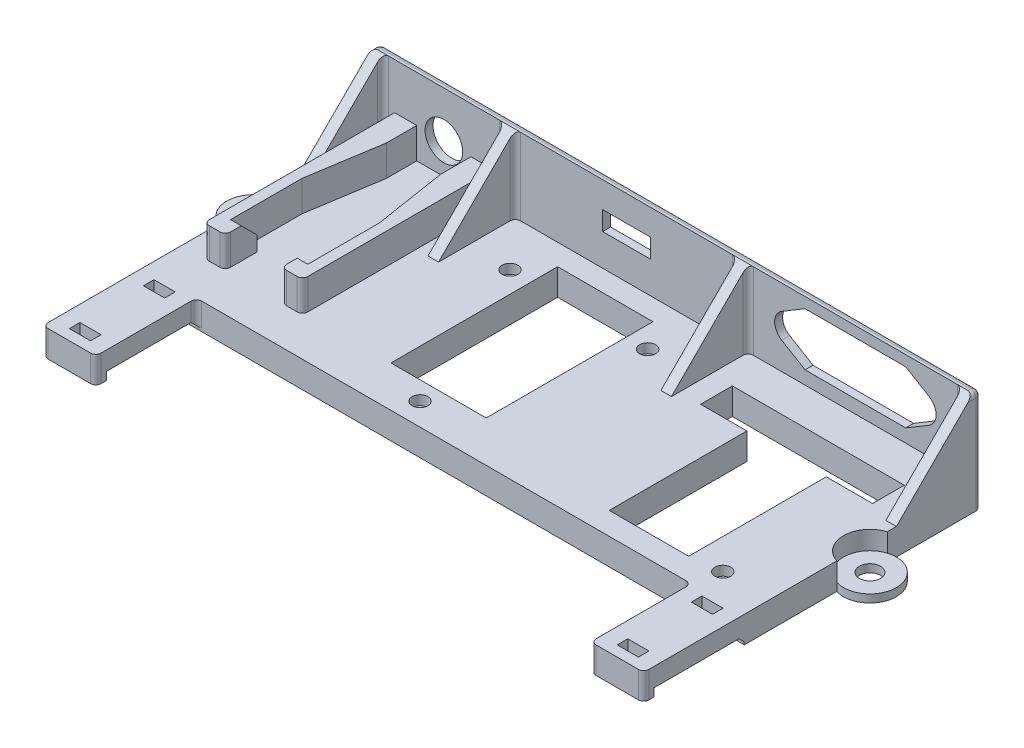
SolidWorks part; units mm, degrees
note: The reader was unsure of these and kept them because the rebuilt part matched: shared geometry of "Sketch1<4>", "Sketch2<3>", "Sketch2<4>", "Sketch2<5>", "Sketch1<5>", "Sketch2<6>", "Sketch4<4>".
ref_plane "Front Plane" through (0, 0, 0) normal (0, 0, 1) x (1, 0, 0)
ref_plane "Top Plane" through (0, 0, 0) normal (0, 1, 0) x (1, 0, 0)
ref_plane "Right Plane" through (0, 0, 0) normal (1, 0, 0) x (0, 0, -1)
sketch "Sketch1" plane through (0, 0, 0) normal (0, 0, 1) x (1, 0, 0)
  line L0 (78.75, 7.5) -> (103.75, 7.5)
  line L1 (0, 0) -> (113.5, 0)
  line L2 (0, 0) -> (0, 14.5)
  line L3 (0, 14.5) -> (113.5, 14.5)
  line L4 (113.5, 0) -> (113.5, 14.5)
  line L5 (100.75, 2.5) -> (105.1621, 5.1402)
  line L6 (75, 14.5) -> (107.5, 14.5)
  line L7 (75, 14.5) -> (75, 0)
  line L8 (75, 0) -> (107.5, 0)
  line L9 (107.5, 14.5) -> (107.5, 0)
  line L10 (81.75, 12.5) -> (100.75, 12.5)
  line L11 (81.75, 12.5) -> (81.75, 2.5)
  line L12 (81.75, 2.5) -> (100.75, 2.5)
  line L13 (100.75, 12.5) -> (100.75, 2.5)
  line L14 (0, 0) -> (113.5, 0)
  line L15 (0, 0) -> (0, -5)
  line L16 (0, -5) -> (113.5, -5)
  line L17 (113.5, 0) -> (113.5, -5)
  line L18 (43.5, 9.6) -> (52.5, 9.6)
  line L19 (43.5, 9.6) -> (43.5, 6)
  line L20 (43.5, 6) -> (52.5, 6)
  line L21 (52.5, 9.6) -> (52.5, 6)
  line L22 (31, 0) -> (65, 0)
  line L23 (31, 0) -> (31, 9.6)
  line L24 (31, 9.6) -> (65, 9.6)
  line L25 (65, 0) -> (65, 9.6)
  line L26 (6, 13) -> (21, 13)
  line L27 (6, 13) -> (6, 0)
  line L28 (6, 0) -> (21, 0)
  line L29 (21, 13) -> (21, 0)
  line L30 (25, 0) -> (27, 0)
  line L31 (25, 0) -> (25, 14.5)
  line L32 (25, 14.5) -> (27, 14.5)
  line L33 (27, 0) -> (27, 14.5)
  line L34 (69, 14.5) -> (71, 14.5)
  line L35 (69, 14.5) -> (69, 0)
  line L36 (69, 0) -> (71, 0)
  line L37 (71, 14.5) -> (71, 0)
  line L38 (0, 14.5) -> (2, 14.5)
  line L39 (0, 14.5) -> (0, 0)
  line L40 (0, 0) -> (2, 0)
  line L41 (2, 14.5) -> (2, 0)
  line L42 (113.5, 14.5) -> (111.5, 14.5)
  line L43 (113.5, 14.5) -> (113.5, 0)
  line L44 (113.5, 0) -> (111.5, 0)
  line L45 (111.5, 14.5) -> (111.5, 0)
  line L46 (100.75, 12.5) -> (105.1621, 9.8598)
  line L47 (81.75, 12.5) -> (77.3379, 9.8598)
  line L48 (81.75, 2.5) -> (77.3379, 5.1402)
  circle A0 centre (78.75, 7.5) radius 1.5
  circle A1 centre (103.75, 7.5) radius 1.5
  circle A2 centre (13.5, 5.8) radius 3.55
  circle A3 centre (103.75, 7.5) radius 2.75
  circle A4 centre (78.75, 7.5) radius 2.75
  point P9 (78.75, 6)
  point P14 (91.25, 7.5)
  point P15 (91.25, 14.5)
  point P20 (81.75, 7.5)
  point P21 (91.25, 12.5)
  point P32 (48, 9.6)
  point P33 (48, 9.6)
  point P36 (13.5, 13)
  point P55 (80.0469, 3.5192)
  dimension "D2" = 3
  dimension "D12" = 7.1
  dimension "D27" = 5.5
  dimension "D1" = 14.5
  dimension "D3" = 6
  dimension "D4" = 25
  dimension "D5" = 32.5
  dimension "D6" = 19
  dimension "D7" = 10
  dimension "D8" = 3.6
  dimension "D9" = 9
  dimension "D10" = 6
  dimension "D11" = 34
  dimension "D13" = 5.8
  dimension "D14" = 13
  dimension "D15" = 15
  dimension "D16" = 2
  dimension "D17" = 2
  dimension "D18" = 2
  dimension "D19" = 4
  dimension "D20" = 5
  dimension "D21" = 4
  dimension "D22" = 4
  dimension "D23" = 4
  dimension "D24" = 4
  dimension "D25" = 4
  dimension "D26" = 2
extrude "Boss-Extrude1" add sketch "Sketch1" against normal blind 1.5
extrude "Boss-Extrude2" add sketch "Sketch1<4>" against normal blind 1.5 and the other way blind 43.25 contours L17 L1 L14 L15 L16
sketch "Sketch1<4>" plane through (0, 0, 0) normal (0, 0, 1) x (1, 0, 0) same geometry as "Sketch1"
sketch "Sketch2" plane through (0, 0, 0) normal (0, 1, 0) x (1, 0, 0)
  line L0 (0, 0) -> (113.5, 0) construction
  line L1 (20.8, 0) -> (6.2, 0)
  line L2 (20.8, 0) -> (20.8, -30)
  line L3 (20.8, -30) -> (6.2, -30)
  line L4 (6.2, 0) -> (6.2, -30)
  line L5 (6, 0) -> (21, 0) construction
  line L6 (35, -9) -> (61, -9)
  line L7 (0, 0) -> (113.5, 0) construction
  line L8 (43.5, 0) -> (52.5, 0) construction
  line L9 (0, 0) -> (113.5, 0) construction
  line L10 (75, 0) -> (107.5, 0)
  line L11 (75, 0) -> (75, -41.3)
  line L12 (75, -41.3) -> (107.5, -41.3)
  line L13 (107.5, 0) -> (107.5, -41.3)
  line L14 (-1.5, -21) -> (115, -21)
  line L15 (0, 1.5) -> (113.5, 1.5) construction
  line L16 (0, 1.5) -> (113.5, 1.5) construction
  line L17 (6.2, -19.5) -> (20.8, -19.5)
  line L18 (39, -4) -> (57, -4)
  line L19 (39, -4) -> (39, -39)
  line L20 (39, -39) -> (57, -39)
  line L21 (57, -4) -> (57, -39)
  line L22 (75, -7) -> (107.5, -7)
  line L23 (75, -7) -> (75, -13)
  line L24 (75, -13) -> (107.5, -13)
  line L25 (107.5, -7) -> (107.5, -13)
  line L26 (83.75, -13) -> (98.75, -13)
  line L27 (83.75, -13) -> (83.75, -39)
  line L28 (83.75, -39) -> (98.75, -39)
  line L29 (98.75, -13) -> (98.75, -39)
  line L30 (8.375, 0) -> (18.625, 0)
  line L31 (8.375, 0) -> (8.375, -5.75)
  line L32 (8.375, -5.75) -> (18.625, -5.75)
  line L33 (18.625, 0) -> (18.625, -5.75)
  line L34 (8.375, -5.75) -> (6.2, -19.5)
  line L35 (18.625, -5.75) -> (20.8, -19.5)
  line L36 (8.2, -34) -> (18.8, -34)
  line L37 (6.2, -34) -> (8.2, -34)
  line L38 (6.2, -34) -> (6.2, -30)
  line L39 (6.2, -30) -> (8.2, -30)
  line L40 (8.2, -34) -> (8.2, -30)
  line L41 (20.8, -34) -> (18.8, -34)
  line L42 (20.8, -34) -> (20.8, -30)
  line L43 (20.8, -30) -> (18.8, -30)
  line L44 (18.8, -34) -> (18.8, -30)
  line L46 (4.2, 0) -> (22.8, 0)
  line L47 (4.2, 0) -> (4.2, -36)
  line L48 (4.2, -36) -> (22.8, -36)
  line L49 (22.8, 0) -> (22.8, -36)
  line L50 (8.2, -34) -> (18.8, -34)
  line L51 (8.2, -34) -> (8.2, -36)
  line L52 (8.2, -36) -> (18.8, -36)
  line L53 (18.8, -34) -> (18.8, -36)
  line L54 (39, -35.5) -> (57, -35.5)
  line L55 (39, -35.5) -> (39, -39)
  line L56 (39, -39) -> (57, -39)
  line L57 (57, -35.5) -> (57, -39)
  circle A0 centre (104.5, -38.3) radius 1.5
  circle A1 centre (35, -9) radius 1.5
  circle A2 centre (61, -9) radius 1.5
  circle A3 centre (48, -39) radius 1.5
  circle A4 centre (-1.5, -21) radius 2
  circle A5 centre (115, -21) radius 2
  circle A6 centre (115, -21) radius 5
  circle A7 centre (-1.5, -21) radius 5
  point P17 (13.5, 0)
  point P20 (13.5, 0)
  point P22 (48, -9)
  point P26 (48, 0)
  point P38 (56.75, 1.5)
  point P39 (56.75, -21)
  point P49 (48, -39)
  point P57 (91.25, -39)
  point P58 (91.25, -41.3)
  point P63 (13.5, 0)
  point P76 (13.5, -36)
  point P77 (13.5, -19.5)
  line M11 (113.5, 0) -> (0, 0)
  line M12 (0, 0) -> (0, -43.25)
  line M14 (113.5, -43.25) -> (113.5, 0)
  dimension "D3" = 3
  dimension "D10" = 4
  dimension "D1" = 14.6
  dimension "D2" = 30
  dimension "D4" = 26
  dimension "D5" = 39
  dimension "D6" = 41.3
  dimension "D7" = 3
  dimension "D8" = 3
  dimension "D9" = 116.5
  dimension "D11" = 22.5
  dimension "D12" = 3
  dimension "D13" = 3
  dimension "D14" = 35
  dimension "D15" = 18
  dimension "D16" = 30
  dimension "D17" = 15
  dimension "D18" = 7
  dimension "D19" = 13
  dimension "D20" = 39
  dimension "D21" = 10.25
  dimension "D22" = 5.75
  dimension "D23" = 10.5
  dimension "D24" = 2
  dimension "D25" = 4
  dimension "D26" = 2
  dimension "D27" = 2
  dimension "D28" = 3.5
extrude "Cut-Extrude1" cut sketch "Sketch2" against normal through all
extrude "Boss-Extrude3" add sketch "Sketch2<3>" against normal up to surface (5 mm away) contours A7 A4 M12 | A6 A5 M14 up to face at (91.25, -5, 18)
sketch "Sketch2<3>" plane through (0, 0, 0) normal (0, 1, 0) x (1, 0, 0) same geometry as "Sketch2"
extrude "Cut-Extrude2" cut sketch "Sketch2<4>" against normal offset from surface (3.5 mm away) 1.5 up to face at (115.25, -5, 21)
sketch "Sketch2<4>" plane through (0, 0, 0) normal (0, 1, 0) x (1, 0, 0) same geometry as "Sketch2"
extrude "Cut-Extrude3" cut sketch "Sketch2<5>" against normal through all contours A4 L14 M12 | L14 A4 M12 | L14 A5 M14 | A5 L14 M14
sketch "Sketch2<5>" plane through (0, 0, 0) normal (0, 1, 0) x (1, 0, 0) same geometry as "Sketch2"
extrude "Boss-Extrude4" add sketch "Sketch1<5>" along normal blind 15 contours L41 L3 L2 L1 | L3 L45 L14 L4 | L33 L32 L31 L30 | L37 L36 L35 L34
sketch "Sketch1<5>" plane through (0, 0, 0) normal (0, 0, 1) x (1, 0, 0) same geometry as "Sketch1"
chamfer "Chamfer1" distance 15 angle 45 4 edges at (112.5, 14.5, 15) (70, 14.5, 15) (26, 14.5, 15) (1, 14.5, 15)
extrude "Boss-Extrude5" add sketch "Sketch2<6>" along normal up to vertex (14.5 mm away) contours L49 L2 L14 M11 | L34 L31 L4 M11 | L47 L14 L4 M11 | L33 L35 L2 M11 | L41 L53 L48 L49 L14 L2 L42 | L51 L37 L38 L4 L14 L47 L48 | L37 L40 L3 L38 | L44 L41 L42 L3
sketch "Sketch2<6>" plane through (0, 0, 0) normal (0, 1, 0) x (1, 0, 0) same geometry as "Sketch2"
sketch "Sketch4" plane through (0, 0, 0) normal (0, 1, 0) x (1, 0, 0)
  line L0 (5, -58.25) -> (5, -46.25)
  line L1 (0, -43.25) -> (10, -43.25)
  line L2 (0, -43.25) -> (0, -62.25)
  line L3 (0, -62.25) -> (10, -62.25)
  line L4 (10, -43.25) -> (10, -62.25)
  line L5 (113.5, -43.25) -> (103.5, -43.25)
  line L6 (113.5, -43.25) -> (113.5, -62.25)
  line L7 (113.5, -62.25) -> (103.5, -62.25)
  line L8 (103.5, -43.25) -> (103.5, -62.25)
  line L9 (3, -46.25) -> (7, -46.25)
  line L10 (3, -46.25) -> (3, -44.25)
  line L11 (3, -44.25) -> (7, -44.25)
  line L12 (7, -46.25) -> (7, -44.25)
  line L13 (3, -58.25) -> (7, -58.25)
  line L14 (3, -58.25) -> (3, -60.25)
  line L15 (3, -60.25) -> (7, -60.25)
  line L16 (7, -58.25) -> (7, -60.25)
  line L17 (108.5, -58.25) -> (108.5, -46.25)
  line L19 (106.5, -46.25) -> (110.5, -46.25)
  line L20 (106.5, -46.25) -> (106.5, -44.25)
  line L21 (106.5, -44.25) -> (110.5, -44.25)
  line L22 (110.5, -46.25) -> (110.5, -44.25)
  line L23 (106.5, -58.25) -> (110.5, -58.25)
  line L24 (106.5, -58.25) -> (106.5, -60.25)
  line L25 (106.5, -60.25) -> (110.5, -60.25)
  line L26 (110.5, -58.25) -> (110.5, -60.25)
  line L27 (0, -62.25) -> (10, -62.25)
  line L28 (0, -62.25) -> (0, -60.25)
  line L29 (0, -60.25) -> (10, -60.25)
  line L30 (10, -62.25) -> (10, -60.25)
  line L31 (113.5, -62.25) -> (103.5, -62.25)
  line L32 (113.5, -62.25) -> (113.5, -60.25)
  line L33 (113.5, -60.25) -> (103.5, -60.25)
  line L34 (103.5, -62.25) -> (103.5, -60.25)
  point P20 (5, -62.25)
  point P21 (108.5, -62.25)
  dimension "D1" = 10
  dimension "D2" = 4
  dimension "D3" = 2
  dimension "D4" = 2
  dimension "D5" = 4
  dimension "D6" = 1
  dimension "D7" = 2
  dimension "D8" = 12
  dimension "D9" = 4
  dimension "D10" = 2
  dimension "D11" = 2
  dimension "D12" = 4
  dimension "D13" = 12
extrude "Boss-Extrude6" add sketch "Sketch4" against normal offset from surface (3.5 mm away) 1.5
extrude "Boss-Extrude7" add sketch "Sketch4<4>" against normal up to surface (5 mm away) contours L29 L2 L3 L4 L15 | L6 L33 L25 L8 L7 up to face at (115, -5, 23)
sketch "Sketch4<4>" plane through (0, 0, 0) normal (0, 1, 0) x (1, 0, 0) same geometry as "Sketch4"
sketch "Sketch5" plane through (0, -3.5, 0) normal (0, -1, 0) x (1, 0, 0)
  line L1 (110.5, 46.25) -> (106.5, 46.25)
  line L2 (110.5, 46.25) -> (110.5, 58.25)
  line L3 (110.5, 58.25) -> (106.5, 58.25)
  line L4 (106.5, 46.25) -> (106.5, 58.25)
  line L5 (7, 46.25) -> (3, 46.25)
  line L6 (7, 46.25) -> (7, 58.25)
  line L7 (7, 58.25) -> (3, 58.25)
  line L8 (3, 46.25) -> (3, 58.25)
extrude "Cut-Extrude4" cut sketch "Sketch5" against normal blind 0.4
chamfer "Chamfer2" distance 1 angle 45 2 edges at (108.5, -3.5, 43.25) (5, -3.5, 43.25)
chamfer "Chamfer3" distance 3 angle 45 2 edges at (7.2, 5.8, 30) (19.8, 5.8, 30)
sketch "Sketch6" plane through (0, -5, 0) normal (0, -1, 0) x (1, 0, 0)
  circle A0 centre (35, 9) radius 3
  circle A1 centre (61, 9) radius 3
  circle A2 centre (48, 39) radius 3
  circle A3 centre (104.5, 38.3) radius 3
  dimension "D1" = 6
extrude "Cut-Extrude6" cut sketch "Sketch6" against normal blind 3
sketch "Sketch7" plane through (0, -2, 0) normal (0, -1, 0) x (1, 0, 0)
  circle A0 centre (48, 39) radius 2.8837
  circle A1 centre (35, 9) radius 3
  circle A2 centre (61, 9) radius 3
  circle A3 centre (104.5, 38.3) radius 3
extrude "Boss-Extrude8" add sketch "Sketch7" against normal blind 0.2
fillet "Fillet1" radius 1 26 edges at (0, 14.5, -0.75) (113.5, 14.5, -0.75) (111.5, 7.25, 0) (69, 7.25, 0) (25, 7.25, 0) (71, 7.25, 0) (27, 7.25, 0) (2, 7.25, 0) (56.75, -5, -1.5) (56.75, 14.5, -1.5) (113.5, 4.75, -1.5) (0, 4.75, -1.5) (103.5, -2.25, 43.25) (103.5, -2.5, 62.25) (113.5, -2.5, 62.25) (10, -2.25, 43.25) (10, -2.5, 62.25) (0, -2.5, 62.25) (18.8, 2.9, 36) (8.2, 2.9, 36) (4.2, 2.9, 36) (22.8, 2.9, 36) (108.5, -3.1, 58.25) (108.5, -3.1, 46.25) (5, -3.1, 58.25) (5, -3.1, 46.25)
equation "\"D5@Sketch2\"=37.5+1.5"
